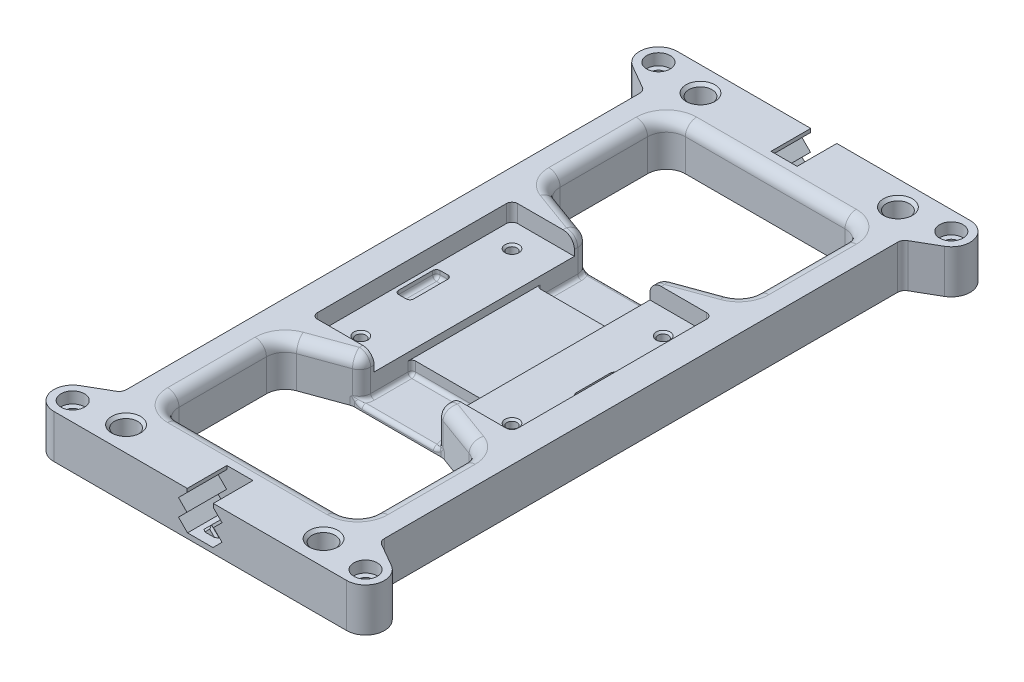
SolidWorks part; units mm, degrees
ref_plane "Front Plane" through (0, 0, 0) normal (0, 0, 1) x (1, 0, 0)
ref_plane "Top Plane" through (0, 0, 0) normal (0, 1, 0) x (1, 0, 0)
ref_plane "Right Plane" through (0, 0, 0) normal (1, 0, 0) x (0, 0, -1)
sketch "Sketch1" plane through (0, 0, 0) normal (0, 1, 0) x (1, 0, 0)
  line L0 (0, 0) -> (0, 67.5) construction
  line L1 (0, 67.5) -> (-34.125, 67.5) construction
  line L2 (-34.125, 67.5) -> (-34.125, 0)
  line L3 (-34.125, 0) -> (34.125, 0)
  line L4 (-34.125, 67.5) -> (-34.125, 80.5)
  line L5 (-32.125, 82.5) -> (32.125, 82.5)
  line L6 (0, 82.5) -> (0, 67.5) construction
  line L9 (34.125, 67.5) -> (34.125, 80.5)
  line L10 (34.125, 67.5) -> (34.125, 0)
  line L14 (-34.125, 70.5) -> (0, 70.5) construction
  circle A1 centre (-26.125, 76) radius 3.075 construction
  arc A11 (-34.125, 80.5) -> (-32.125, 82.5) centre (-32.125, 80.5) cw
  circle A12 centre (26.125, 76) radius 3.075 construction
  arc A13 (34.125, 80.5) -> (32.125, 82.5) centre (32.125, 80.5) ccw
  point P19 (34.125, 82.5)
  point P45 (-34.125, 82.5)
  dimension "D5" = 12
  dimension "D3" = 6.15
  dimension "D4" = 2
  dimension "D1" = 34.125
  dimension "D2" = 67.5
  dimension "D6" = 8
  dimension "D7" = 8.5
  dimension "D8" = 3
  dimension "D11" = 82.5
extrude "Boss-Extrude1" add sketch "Sketch1" along normal blind 11.5
sketch "Sketch3" plane through (0, 11.5, 0) normal (0, 1, 0) x (1, 0, 0)
  line L0 (0, 0) -> (-34.125, 0) construction
  line L2 (0, 0) -> (0, 82.5) construction
  line L3 (32.125, 82.5) -> (-32.125, 82.5) construction
  line L4 (3.96, -16.3) -> (3.96, 16.3)
  line L5 (-2.46, -17.8) -> (2.46, -17.8)
  line L6 (-3.96, 16.3) -> (-3.96, -16.3)
  line L7 (2.46, 17.8) -> (-2.46, 17.8)
  line L8 (0, 17.8) -> (0, -17.8) construction
  line L9 (-34.125, 80.5) -> (-34.125, 0) construction
  line L10 (-34.125, 0) -> (34.125, 0) construction
  arc A0 (-2.46, 17.8) -> (-3.96, 16.3) centre (-2.46, 16.3) ccw
  arc A1 (3.96, 16.3) -> (2.46, 17.8) centre (2.46, 16.3) ccw
  arc A2 (2.46, -17.8) -> (3.96, -16.3) centre (2.46, -16.3) ccw
  arc A3 (-3.96, -16.3) -> (-2.46, -17.8) centre (-2.46, -16.3) ccw
  point P9 (0, 0)
  point P23 (0, 0)
  dimension "D2" = 1.5
  dimension "D1" = 35.6
  dimension "D3" = 7.92
sketch "Sketch4" plane through (0, 11.5, 0) normal (0, 1, 0) x (1, 0, 0)
  circle A3 centre (26.125, 76) radius 3.075 construction
  circle A5 centre (-26.125, 76) radius 3.075 construction
  circle A10 centre (26.125, 76) radius 3.075
  circle A13 centre (-26.125, 76) radius 3.075
extrude "Cut-Extrude1" cut sketch "Sketch4" against normal blind 6
sketch "Sketch40" plane through (0, 0, -82.5) normal (0, 0, -1) x (-1, 0, 0)
  line L1 (5.55, 3.75) -> (3.3, 6) construction
  line L2 (5.55, 3.75) -> (3.3, 1.5) construction
  line L3 (0, 11.5) -> (0, 1.5) construction
  line L4 (0, 1.5) -> (3.3, 1.5) construction
  line L5 (3.3, 6) -> (5.55, 8.25) construction
  line L6 (3.3, 6) -> (3.3, 1.5) construction
  line L7 (5.55, 8.25) -> (3.3, 10.5) construction
  line L8 (3.3, 6) -> (3.3, 10.5) construction
  line L9 (5.55, 3.75) -> (5.55, 8.25) construction
  line L10 (3.3, 10.5) -> (3.3, 11.5) construction
  line L11 (3.3, 1.5) -> (5.55, 1.5) construction
  line L12 (5.55, 1.5) -> (5.55, 3.75) construction
  line L13 (5.55, 3.75) -> (3.3, 3.75) construction
  line L14 (5.55, 8.25) -> (3.3, 8.25) construction
  line L15 (3.3, 6) -> (5.55, 6) construction
  line L16 (-3.3, 11.5) -> (3.3, 11.5)
  line L17 (3.3621, 1.35) -> (-3.3621, 1.35)
  line L18 (0, 1.35) -> (0, 1.5) construction
  line L19 (-3.3, 11.5) -> (-3.45, 11.5)
  line L20 (-3.45, 10.5621) -> (-3.45, 11.5)
  line L22 (3.45, 10.5621) -> (3.45, 11.5)
  line L23 (5.7621, 8.25) -> (3.45, 10.5621)
  line L24 (3.5121, 6) -> (5.7621, 8.25)
  line L25 (5.7621, 3.75) -> (3.5121, 6)
  line L26 (5.7621, 3.75) -> (3.3621, 1.35)
  line L33 (3.3, 11.5) -> (3.45, 11.5)
  line L34 (-32.125, 11.5) -> (32.125, 11.5) construction
  line L35 (-5.7621, 8.25) -> (-3.45, 10.5621)
  line L36 (-3.5121, 6) -> (-5.7621, 8.25)
  line L37 (-5.7621, 3.75) -> (-3.5121, 6)
  line L38 (-5.7621, 3.75) -> (-3.3621, 1.35)
  dimension "D2" = 1
  dimension "D3" = 45
  dimension "D4" = 45
  dimension "D5" = 45
  dimension "D6" = 45
  dimension "D7" = 3.3
  dimension "D1" = 10
  dimension "D8" = 0.15
  dimension "D9" = 0.15
  dimension "D10" = 0.15
  dimension "D11" = 0.15
  dimension "D12" = 0.15
  dimension "D13" = 0.15
extrude "Cut-Extrude31" cut sketch "Sketch40" against normal blind 10.5
sketch "Sketch41" plane through (0, 0, -72) normal (0, 0, -1) x (-1, 0, 0)
  line L0 (0, 1.35) -> (0, 3.35) construction
  line L1 (-3.3621, 1.35) -> (3.3621, 1.35) construction
  line L2 (0, 3.35) -> (2, 1.35)
  line L3 (-3.3621, 1.35) -> (3.3621, 1.35) construction
  line L4 (2, 1.35) -> (-2, 1.35)
  line L5 (0, 3.35) -> (-2, 1.35)
  dimension "D1" = 45
  dimension "D2" = 2
extrude "Boss-Extrude9" add sketch "Sketch41" along normal blind 8
chamfer "Chamfer7" distance 0.5 angle 45 2 edges at (1, 2.35, -80) (-1, 2.35, -80)
mirror "Mirror1" about plane through (0, 0, 0) normal (0, 0, 1) of "Cut-Extrude1", "Boss-Extrude1", "Cut-Extrude31", "Boss-Extrude9", "Chamfer7"
sketch "Sketch28" plane through (0, 11.5, 0) normal (0, 1, 0) x (1, 0, 0)
  line L1 (-26, 26) -> (26, 26) construction
  line L2 (-26, 26) -> (-26, -26) construction
  line L3 (-26, -26) -> (26, -26) construction
  line L4 (26, 26) -> (26, -26) construction
  line L5 (-26, 26) -> (26, -26) construction
  line L6 (-26, -26) -> (26, 26) construction
  line L7 (-25, 26.5) -> (25, 26.5)
  line L8 (-26.5, 25) -> (-26.5, -25)
  line L9 (-25, -26.5) -> (25, -26.5)
  line L10 (26.5, 25) -> (26.5, -25)
  line L11 (-26.5, 26.5) -> (26.5, -26.5) construction
  line L12 (-26.5, -26.5) -> (26.5, 26.5) construction
  arc A0 (-25, -26.5) -> (-26.5, -25) centre (-25, -25) cw
  arc A1 (25, -26.5) -> (26.5, -25) centre (25, -25) ccw
  arc A2 (25, 26.5) -> (26.5, 25) centre (25, 25) cw
  arc A3 (-25, 26.5) -> (-26.5, 25) centre (-25, 25) ccw
  point P0 (0, 0)
  point P6 (0, 0)
  dimension "D4" = 1.5
  dimension "D1" = 52
  dimension "D2" = 0.5
  dimension "D3" = 0.5
extrude "Cut-Extrude21" cut sketch "Sketch28" against normal blind 4.6
sketch "Sketch36" plane through (0, 6.9, 0) normal (0, 1, 0) x (1, 0, 0)
  line L2 (-26, 26) -> (-26, -26) construction
  line L3 (-26, 26) -> (26, 26) construction
  circle A0 centre (-20, 20) radius 1.35
  circle A1 centre (20, 20) radius 1.35
  circle A2 centre (20, -20) radius 1.35
  circle A3 centre (-20, -20) radius 1.35
  point P15 (0, 0)
  dimension "D3" = 2.7
  dimension "D1" = 6
  dimension "D2" = 6
extrude "Cut-Extrude28" cut sketch "Sketch36" against normal blind 5
chamfer "Chamfer6" distance 0.5 angle 45 4 edges at (-20, 6.9, 21.35) (20, 6.9, 21.35) (20, 6.9, -18.65) (-20, 6.9, -18.65)
sketch "Sketch29" plane through (0, 6.9, 0) normal (0, 1, 0) x (1, 0, 0)
  line L0 (0, 0) -> (26.5, 0) construction
  line L5 (0, 0) -> (0, -26.5) construction
  line L6 (-25, -26.5) -> (25, -26.5) construction
  line L7 (26.5, -25) -> (26.5, 25) construction
  line L8 (-10, 26.5) -> (10, 16.5) construction
  line L9 (-10, 16.5) -> (10, 26.5) construction
  line L10 (-10, -16.5) -> (10, -16.5)
  line L11 (-10, -16.5) -> (-10, -26.5)
  line L12 (-10, -26.5) -> (10, -26.5)
  line L13 (10, -16.5) -> (10, -26.5)
  line L14 (-10, -16.5) -> (10, -26.5) construction
  line L15 (-10, -26.5) -> (10, -16.5) construction
  line L16 (10, 16.5) -> (10, 26.5)
  line L17 (-10, 26.5) -> (10, 26.5)
  line L18 (-10, 16.5) -> (-10, 26.5)
  line L19 (-10, 16.5) -> (10, 16.5)
  point P4 (0, -21.5)
  point P17 (0, 21.5)
  dimension "D1" = 20
  dimension "D2" = 10
extrude "Cut-Extrude22" cut sketch "Sketch29" against normal blind 5.5
sketch "Sketch25" plane through (0, 0, 0) normal (0, -1, 0) x (1, 0, 0)
  line L0 (0, 0) -> (34.125, 0) construction
  line L2 (0, 0) -> (0, 82.5) construction
  line L4 (41.25, 73.1699) -> (35.125, 69.6336)
  line L5 (38.75, 77.5) -> (34.125, 77.5) construction
  line L6 (34.125, 67.9016) -> (34.125, 80.5)
  line L8 (32.125, 82.5) -> (38.75, 82.5)
  line L9 (-38.75, 77.5) -> (-34.125, 77.5) construction
  line L10 (-32.125, 82.5) -> (-38.75, 82.5)
  line L11 (-34.125, 67.9016) -> (-34.125, 80.5)
  line L12 (-41.25, 73.1699) -> (-35.125, 69.6336)
  line L13 (-38.75, -77.5) -> (-34.125, -77.5) construction
  line L14 (38.75, -77.5) -> (34.125, -77.5) construction
  line L15 (-41.25, -73.1699) -> (-35.125, -69.6336)
  line L16 (-34.125, -67.9016) -> (-34.125, -80.5)
  line L17 (-32.125, -82.5) -> (-38.75, -82.5)
  line L18 (32.125, -82.5) -> (38.75, -82.5)
  line L19 (34.125, -67.9016) -> (34.125, -80.5)
  line L20 (41.25, -73.1699) -> (35.125, -69.6336)
  line L21 (34.125, 80.5) -> (34.125, -80.5) construction
  line L22 (32.125, 82.5) -> (-32.125, 82.5) construction
  circle A0 centre (38.75, 77.5) radius 1.7
  arc A1 (41.25, 73.1699) -> (38.75, 82.5) centre (38.75, 77.5) ccw
  arc A2 (35.125, 69.6336) -> (34.125, 67.9016) centre (36.125, 67.9016) ccw
  arc A17 (34.125, 80.5) -> (32.125, 82.5) centre (32.125, 80.5) ccw
  arc A18 (-34.125, 80.5) -> (-32.125, 82.5) centre (-32.125, 80.5) cw
  arc A19 (-35.125, 69.6336) -> (-34.125, 67.9016) centre (-36.125, 67.9016) cw
  arc A20 (-41.25, 73.1699) -> (-38.75, 82.5) centre (-38.75, 77.5) cw
  circle A21 centre (-38.75, 77.5) radius 1.7
  circle A22 centre (-38.75, -77.5) radius 1.7
  arc A23 (-41.25, -73.1699) -> (-38.75, -82.5) centre (-38.75, -77.5) ccw
  arc A24 (-35.125, -69.6336) -> (-34.125, -67.9016) centre (-36.125, -67.9016) ccw
  arc A25 (-34.125, -80.5) -> (-32.125, -82.5) centre (-32.125, -80.5) ccw
  arc A26 (34.125, -80.5) -> (32.125, -82.5) centre (32.125, -80.5) cw
  arc A27 (35.125, -69.6336) -> (34.125, -67.9016) centre (36.125, -67.9016) cw
  arc A28 (41.25, -73.1699) -> (38.75, -82.5) centre (38.75, -77.5) cw
  circle A29 centre (38.75, -77.5) radius 1.7
  arc A30 (34.125, 80.5) -> (32.125, 82.5) centre (32.125, 80.5) ccw construction
  dimension "D1" = 3.4
  dimension "D2" = 10
  dimension "D6" = 2
  dimension "D3" = 4.625
  dimension "D4" = 60
extrude "Boss-Extrude7" add sketch "Sketch25" against normal up to surface (11.5 mm away) up to face at (0, 11.5, 0)
sketch "Sketch27" plane through (0, 11.5, 0) normal (0, 1, 0) x (1, 0, 0)
  circle A4 centre (-38.75, -77.5) radius 3.1
  circle A5 centre (38.75, -77.5) radius 3.1
  circle A6 centre (-38.75, 77.5) radius 3.1
  circle A7 centre (38.75, 77.5) radius 3.1
  dimension "D1" = 6.2
extrude "Cut-Extrude20" cut sketch "Sketch27" against normal blind 3
sketch "Sketch37" plane through (0, 6.9, 0) normal (0, 1, 0) x (1, 0, 0)
  line L0 (34.125, 0) -> (0, 0) construction
  line L2 (0, 0) -> (-34.125, 0) construction
  line L3 (26.5, -25) -> (26.5, 25) construction
  line L4 (24.5, 5.5) -> (22.5, 5.5)
  line L5 (25.5, 4.5) -> (25.5, -4.5)
  line L6 (24.5, -5.5) -> (22.5, -5.5)
  line L7 (21.5, 4.5) -> (21.5, -4.5)
  line L8 (25.5, 5.5) -> (21.5, -5.5) construction
  line L9 (25.5, -5.5) -> (21.5, 5.5) construction
  line L10 (0, 0) -> (0, 26.5) construction
  line L11 (-10, 16.5) -> (10, 16.5) construction
  line L12 (-24.5, -5.5) -> (-22.5, -5.5)
  line L13 (-25.5, 4.5) -> (-25.5, -4.5)
  line L14 (-24.5, 5.5) -> (-22.5, 5.5)
  line L15 (-21.5, 4.5) -> (-21.5, -4.5)
  line L21 (10, 16.5) -> (10, -16.5)
  line L23 (25, 26.5) -> (-25, 26.5) construction
  line L24 (-10, 16.5) -> (10, 16.5)
  line L25 (-10, 16.5) -> (-10, -16.5)
  line L26 (-10, -16.5) -> (10, -16.5)
  line L27 (34.125, -67.9016) -> (34.125, 67.9016) construction
  arc A0 (22.5, -5.5) -> (21.5, -4.5) centre (22.5, -4.5) cw
  arc A1 (25.5, -4.5) -> (24.5, -5.5) centre (24.5, -4.5) cw
  arc A2 (22.5, 5.5) -> (21.5, 4.5) centre (22.5, 4.5) ccw
  arc A3 (24.5, 5.5) -> (25.5, 4.5) centre (24.5, 4.5) cw
  arc A4 (-22.5, 5.5) -> (-21.5, 4.5) centre (-22.5, 4.5) cw
  arc A5 (-24.5, 5.5) -> (-25.5, 4.5) centre (-24.5, 4.5) ccw
  arc A6 (-22.5, -5.5) -> (-21.5, -4.5) centre (-22.5, -4.5) ccw
  arc A7 (-25.5, -4.5) -> (-24.5, -5.5) centre (-24.5, -4.5) ccw
  point P5 (23.5, 0)
  point P54 (10, 0)
  point P56 (-10, 0)
  dimension "D4" = 1
  dimension "D1" = 11
  dimension "D2" = 4
  dimension "D3" = 3
extrude "Cut-Extrude29" cut sketch "Sketch37" against normal blind 2
fillet "Fillet20" radius 1 16 edges at (25.2071, 4.9, -5.2071) (25.5, 4.9, 0) (25.2071, 4.9, 5.2071) (23.5, 4.9, 5.5) (21.7929, 4.9, 5.2071) (21.5, 4.9, 0) (21.7929, 4.9, -5.2071) (-21.7929, 4.9, -5.2071) (-21.5, 4.9, 0) (-21.7929, 4.9, 5.2071) (-23.5, 4.9, 5.5) (-25.2071, 4.9, 5.2071) (-25.5, 4.9, 0) (-25.2071, 4.9, -5.2071) (23.5, 4.9, -5.5) (-23.5, 4.9, -5.5)
sketch "Sketch38" plane through (0, 11.5, 0) normal (0, 1, 0) x (1, 0, 0)
  line L0 (11.9739, -30.2185) -> (22.8351, -34.1716)
  line L1 (26.125, -38.8701) -> (26.125, -62)
  line L2 (21.125, -67) -> (-21.125, -67)
  line L3 (0, -67) -> (0, -26.5) construction
  line L4 (-10, -26.5) -> (10, -26.5) construction
  line L7 (-3.45, -72) -> (3.45, -72) construction
  line L9 (-25, -26.5) -> (25, -26.5) construction
  line L12 (0, 0) -> (34.125, 0) construction
  line L13 (0, 67) -> (0, 26.5) construction
  line L20 (10, -27.3994) -> (10, -26.5)
  line L21 (10, -26.5) -> (25, -26.5) construction
  line L22 (10, -26.5) -> (-10, -26.5)
  line L23 (10, -26.5) -> (10, 26.5) construction
  line L24 (-10, -27.3994) -> (-10, -26.5)
  line L25 (-26.125, -38.8701) -> (-26.125, -62)
  line L26 (-11.9739, -30.2185) -> (-22.8351, -34.1716)
  line L35 (34.125, -67.9016) -> (34.125, 67.9016) construction
  line L36 (-11.9739, 30.2185) -> (-22.8351, 34.1716)
  line L37 (-26.125, 38.8701) -> (-26.125, 62)
  line L38 (-10, 27.3994) -> (-10, 26.5)
  line L39 (10, 26.5) -> (-10, 26.5)
  line L40 (10, 27.3994) -> (10, 26.5)
  line L41 (21.125, 67) -> (-21.125, 67)
  line L42 (26.125, 38.8701) -> (26.125, 62)
  line L43 (11.9739, 30.2185) -> (22.8351, 34.1716)
  arc A0 (26.125, -38.8701) -> (22.8351, -34.1716) centre (21.125, -38.8701) ccw
  arc A1 (26.125, -62) -> (21.125, -67) centre (21.125, -62) cw
  arc A8 (11.9739, -30.2185) -> (10, -27.3994) centre (13, -27.3994) cw
  arc A9 (-11.9739, -30.2185) -> (-10, -27.3994) centre (-13, -27.3994) ccw
  arc A10 (-26.125, -62) -> (-21.125, -67) centre (-21.125, -62) ccw
  arc A11 (-26.125, -38.8701) -> (-22.8351, -34.1716) centre (-21.125, -38.8701) cw
  arc A18 (-26.125, 38.8701) -> (-22.8351, 34.1716) centre (-21.125, 38.8701) ccw
  arc A19 (-26.125, 62) -> (-21.125, 67) centre (-21.125, 62) cw
  arc A20 (-11.9739, 30.2185) -> (-10, 27.3994) centre (-13, 27.3994) cw
  arc A21 (11.9739, 30.2185) -> (10, 27.3994) centre (13, 27.3994) ccw
  arc A22 (26.125, 62) -> (21.125, 67) centre (21.125, 62) ccw
  arc A23 (26.125, 38.8701) -> (22.8351, 34.1716) centre (21.125, 38.8701) cw
  point P49 (10, -29.5)
  point P60 (-10, -29.5)
  point P66 (-10, 29.5)
  point P67 (10, 29.5)
  dimension "D4" = 5
  dimension "D6" = 3
  dimension "D1" = 5
  dimension "D2" = 8
  dimension "D3" = 20
  dimension "D5" = 3
extrude "Cut-Extrude30" cut sketch "Sketch38" against normal through all
sketch "Sketch39" plane through (0, 0, 0) normal (0, -1, 0) x (1, 0, 0)
  line L0 (0, 0) -> (34.125, 0) construction
  line L2 (-11.9739, 30.2185) -> (11.9739, 30.2185)
  line L3 (10, 27.3994) -> (10, 26.5) construction
  line L4 (10, 26.5) -> (-10, 26.5) construction
  line L5 (-10, 26.5) -> (-10, 27.3994) construction
  line L6 (10, 27.3994) -> (10, 26.5)
  line L7 (10, 26.5) -> (-10, 26.5)
  line L8 (-10, 26.5) -> (-10, 27.3994)
  line L9 (-10, -26.5) -> (-10, -27.3994)
  line L10 (10, -26.5) -> (-10, -26.5)
  line L11 (10, -27.3994) -> (10, -26.5)
  line L12 (-11.9739, -30.2185) -> (11.9739, -30.2185)
  line L13 (34.125, 67.9016) -> (34.125, -67.9016) construction
  arc A0 (11.9739, 30.2185) -> (10, 27.3994) centre (13, 27.3994) ccw construction
  arc A1 (-10, 27.3994) -> (-11.9739, 30.2185) centre (-13, 27.3994) ccw construction
  arc A2 (11.9739, 30.2185) -> (10, 27.3994) centre (13, 27.3994) ccw
  arc A3 (-10, 27.3994) -> (-11.9739, 30.2185) centre (-13, 27.3994) ccw
  arc A4 (-10, -27.3994) -> (-11.9739, -30.2185) centre (-13, -27.3994) cw
  arc A5 (11.9739, -30.2185) -> (10, -27.3994) centre (13, -27.3994) cw
extrude "Boss-Extrude8" add sketch "Sketch39" against normal up to surface (1.4 mm away) up to face at (0, 1.4, 21.5)
fillet "Fillet21" radius 1 14 edges at (0, 1.4, -16.5) (0, 1.4, 16.5) (-10.5425, 1.4, 29.1201) (10.5425, 1.4, 29.1201) (-10, 3.15, 16.5) (-10, 1.4, 21.9497) (10, 3.15, 16.5) (10, 1.4, 21.9497) (-10, 1.4, -21.9497) (-10, 3.15, -16.5) (10, 3.15, -16.5) (10, 1.4, -21.9497) (-10.5425, 1.4, -29.1201) (10.5425, 1.4, -29.1201)
fillet "Fillet22" radius 3 26 edges at (-10, 11.5, 26.9497) (-10.5425, 11.5, 29.1201) (10, 11.5, 26.9497) (10.5425, 11.5, 29.1201) (17.4045, 11.5, 32.195) (25.2208, 11.5, 36.0022) (26.125, 11.5, 50.435) (24.6605, 11.5, 65.5355) (0, 11.5, 67) (-24.6605, 11.5, 65.5355) (-26.125, 11.5, 50.435) (-25.2208, 11.5, 36.0022) (-17.4045, 11.5, 32.195) (10, 11.5, -26.9497) (10.5425, 11.5, -29.1201) (17.4045, 11.5, -32.195) (25.2208, 11.5, -36.0022) (26.125, 11.5, -50.435) (24.6605, 11.5, -65.5355) (0, 11.5, -67) (-24.6605, 11.5, -65.5355) (-26.125, 11.5, -50.435) (-25.2208, 11.5, -36.0022) (-10, 11.5, -26.9497) (-10.5425, 11.5, -29.1201) (-17.4045, 11.5, -32.195)
fillet "Fillet24" radius 3 4 edges at (-11.9739, 1.2, 30.2185) (11.9739, 1.2, 30.2185) (11.9739, 1.2, -30.2185) (-11.9739, 1.2, -30.2185)
fillet "Fillet25" radius 1 10 edges at (0, 1.4, 30.2185) (0, 1.4, -30.2185) (12.1079, 2.1665, 30.2926) (10.8141, 1.4985, 30.2185) (-12.1976, 2.1847, 30.3144) (-10.9036, 1.5265, 30.2185) (-10.8141, 1.4985, -30.2185) (10.9036, 1.5265, -30.2185) (-12.1079, 2.1665, -30.2926) (12.1976, 2.1847, -30.3144)
chamfer "Chamfer8" distance 0.75 angle 45 4 edges at (-26.125, 11.5, 72.925) (26.125, 11.5, 72.925) (-26.125, 11.5, -72.925) (26.125, 11.5, -72.925)
sketch "Sketch42" plane through (0, 0, 0) normal (0, 1, 0) x (1, 0, 0)
  line L0 (34.125, -67.9016) -> (34.125, 67.9016) construction
  line L1 (21.125, 67) -> (-21.125, 67) construction
  line L2 (34.125, -67.9016) -> (34.125, 67.9016)
  line L3 (21.125, 67) -> (-21.125, 67)
  line L4 (-35.125, 69.6336) -> (-41.25, 73.1699) construction
  line L5 (38.75, 82.5) -> (-38.75, 82.5) construction
  line L6 (41.25, 73.1699) -> (35.125, 69.6336) construction
  line L7 (35.125, -69.6336) -> (41.25, -73.1699) construction
  line L8 (38.75, -82.5) -> (-38.75, -82.5) construction
  line L9 (-41.25, -73.1699) -> (-35.125, -69.6336) construction
  line L10 (-34.125, 67.9016) -> (-34.125, -67.9016) construction
  line L11 (26.125, 38.8701) -> (26.125, 62) construction
  line L12 (12.471, 30.3994) -> (22.8351, 34.1716) construction
  line L13 (-26.125, 62) -> (-26.125, 38.8701) construction
  line L14 (-11.445, 30.2185) -> (11.445, 30.2185) construction
  line L15 (-22.8351, 34.1716) -> (-12.471, 30.3994) construction
  line L16 (11.9739, 30.2185) -> (22.8351, 34.1716) construction
  line L17 (26.125, 38.8701) -> (26.125, 62) construction
  line L18 (-35.125, 69.6336) -> (-41.25, 73.1699)
  line L19 (38.75, 82.5) -> (-38.75, 82.5)
  line L20 (41.25, 73.1699) -> (35.125, 69.6336)
  line L21 (35.125, -69.6336) -> (41.25, -73.1699)
  line L22 (38.75, -82.5) -> (-38.75, -82.5)
  line L23 (-41.25, -73.1699) -> (-35.125, -69.6336)
  line L24 (-34.125, 67.9016) -> (-34.125, -67.9016)
  line L25 (26.125, 38.8701) -> (26.125, 62)
  line L26 (12.471, 30.3994) -> (22.8351, 34.1716)
  line L27 (-26.125, 62) -> (-26.125, 38.8701)
  line L28 (-11.445, 30.2185) -> (11.445, 30.2185)
  line L29 (-22.8351, 34.1716) -> (-12.471, 30.3994)
  line L30 (11.9739, 30.2185) -> (22.8351, 34.1716)
  line L31 (26.125, 38.8701) -> (26.125, 62)
  line L32 (22.8351, -34.1716) -> (12.471, -30.3994) construction
  line L33 (26.125, -62) -> (26.125, -38.8701) construction
  line L34 (-12.471, -30.3994) -> (-22.8351, -34.1716) construction
  line L35 (-21.125, -67) -> (21.125, -67) construction
  line L36 (11.445, -30.2185) -> (-11.445, -30.2185) construction
  line L37 (22.8351, -34.1716) -> (12.471, -30.3994)
  line L38 (26.125, -62) -> (26.125, -38.8701)
  line L39 (-12.471, -30.3994) -> (-22.8351, -34.1716)
  line L40 (-21.125, -67) -> (21.125, -67)
  line L41 (11.445, -30.2185) -> (-11.445, -30.2185)
  line L42 (-26.125, -38.8701) -> (-26.125, -62) construction
  line L43 (-26.125, -38.8701) -> (-26.125, -62)
  arc A0 (-34.125, 67.9016) -> (-35.125, 69.6336) centre (-36.125, 67.9016) ccw construction
  arc A1 (-38.75, 82.5) -> (-41.25, 73.1699) centre (-38.75, 77.5) ccw construction
  arc A2 (41.25, 73.1699) -> (38.75, 82.5) centre (38.75, 77.5) ccw construction
  arc A3 (34.125, -67.9016) -> (35.125, -69.6336) centre (36.125, -67.9016) ccw construction
  circle A4 centre (38.75, -77.5) radius 1.7 construction
  arc A5 (38.75, -82.5) -> (41.25, -73.1699) centre (38.75, -77.5) ccw construction
  circle A6 centre (-38.75, -77.5) radius 1.7 construction
  arc A7 (-41.25, -73.1699) -> (-38.75, -82.5) centre (-38.75, -77.5) ccw construction
  arc A8 (-35.125, -69.6336) -> (-34.125, -67.9016) centre (-36.125, -67.9016) ccw construction
  arc A9 (26.125, 62) -> (21.125, 67) centre (21.125, 62) ccw construction
  arc A10 (-21.125, 67) -> (-26.125, 62) centre (-21.125, 62) ccw construction
  arc A11 (22.8351, 34.1716) -> (26.125, 38.8701) centre (21.125, 38.8701) ccw construction
  arc A12 (11.445, 30.2185) -> (12.471, 30.3994) centre (11.445, 33.2185) ccw construction
  arc A13 (-26.125, 38.8701) -> (-22.8351, 34.1716) centre (-21.125, 38.8701) ccw construction
  arc A14 (-12.471, 30.3994) -> (-11.445, 30.2185) centre (-11.445, 33.2185) ccw construction
  arc A15 (22.8351, 34.1716) -> (26.125, 38.8701) centre (21.125, 38.8701) ccw construction
  arc A16 (26.125, 62) -> (21.125, 67) centre (21.125, 62) ccw construction
  arc A17 (-34.125, 67.9016) -> (-35.125, 69.6336) centre (-36.125, 67.9016) ccw
  arc A18 (-38.75, 82.5) -> (-41.25, 73.1699) centre (-38.75, 77.5) ccw
  arc A19 (41.25, 73.1699) -> (38.75, 82.5) centre (38.75, 77.5) ccw
  arc A20 (34.125, -67.9016) -> (35.125, -69.6336) centre (36.125, -67.9016) ccw
  circle A21 centre (38.75, -77.5) radius 1.7
  arc A22 (38.75, -82.5) -> (41.25, -73.1699) centre (38.75, -77.5) ccw
  circle A23 centre (-38.75, -77.5) radius 1.7
  arc A24 (-41.25, -73.1699) -> (-38.75, -82.5) centre (-38.75, -77.5) ccw
  arc A25 (-35.125, -69.6336) -> (-34.125, -67.9016) centre (-36.125, -67.9016) ccw
  arc A26 (26.125, 62) -> (21.125, 67) centre (21.125, 62) ccw
  arc A27 (-21.125, 67) -> (-26.125, 62) centre (-21.125, 62) ccw
  arc A28 (22.8351, 34.1716) -> (26.125, 38.8701) centre (21.125, 38.8701) ccw
  arc A29 (11.445, 30.2185) -> (12.471, 30.3994) centre (11.445, 33.2185) ccw
  arc A30 (-26.125, 38.8701) -> (-22.8351, 34.1716) centre (-21.125, 38.8701) ccw
  arc A31 (-12.471, 30.3994) -> (-11.445, 30.2185) centre (-11.445, 33.2185) ccw
  arc A32 (22.8351, 34.1716) -> (26.125, 38.8701) centre (21.125, 38.8701) ccw
  arc A33 (26.125, 62) -> (21.125, 67) centre (21.125, 62) ccw
  circle A34 centre (-38.75, 77.5) radius 1.7 construction
  circle A35 centre (38.75, 77.5) radius 1.7 construction
  circle A36 centre (-38.75, 77.5) radius 1.7
  circle A37 centre (38.75, 77.5) radius 1.7
  arc A38 (-11.445, -30.2185) -> (-12.471, -30.3994) centre (-11.445, -33.2185) ccw construction
  arc A39 (12.471, -30.3994) -> (11.445, -30.2185) centre (11.445, -33.2185) ccw construction
  arc A40 (26.125, -38.8701) -> (22.8351, -34.1716) centre (21.125, -38.8701) ccw construction
  arc A41 (21.125, -67) -> (26.125, -62) centre (21.125, -62) ccw construction
  arc A42 (-22.8351, -34.1716) -> (-26.125, -38.8701) centre (-21.125, -38.8701) ccw construction
  arc A43 (-26.125, -62) -> (-21.125, -67) centre (-21.125, -62) ccw construction
  arc A44 (-11.445, -30.2185) -> (-12.471, -30.3994) centre (-11.445, -33.2185) ccw
  arc A45 (12.471, -30.3994) -> (11.445, -30.2185) centre (11.445, -33.2185) ccw
  arc A46 (26.125, -38.8701) -> (22.8351, -34.1716) centre (21.125, -38.8701) ccw
  arc A47 (21.125, -67) -> (26.125, -62) centre (21.125, -62) ccw
  arc A48 (-22.8351, -34.1716) -> (-26.125, -38.8701) centre (-21.125, -38.8701) ccw
  arc A49 (-26.125, -62) -> (-21.125, -67) centre (-21.125, -62) ccw
  arc A50 (35.125, 69.6336) -> (34.125, 67.9016) centre (36.125, 67.9016) ccw construction
  arc A51 (35.125, 69.6336) -> (34.125, 67.9016) centre (36.125, 67.9016) ccw
  dimension "D6" = 3.4
  dimension "D1" = 155
  dimension "D2" = 77.5
  dimension "D3" = 52.25
  dimension "D4" = 36.7815
  dimension "D5" = 36.7815
equation "\"D3@Sketch28\"=\"D2@Sketch28\""
equation "\"D2@Sketch36\"=\"D1@Sketch36\""
equation "\"D9@Sketch40\"=\"D8@Sketch40\""
equation "\"D10@Sketch40\"=\"D8@Sketch40\""
equation "\"D11@Sketch40\"=\"D8@Sketch40\""
equation "\"D12@Sketch40\"=\"D8@Sketch40\""
equation "\"D13@Sketch40\"=\"D8@Sketch40\""
